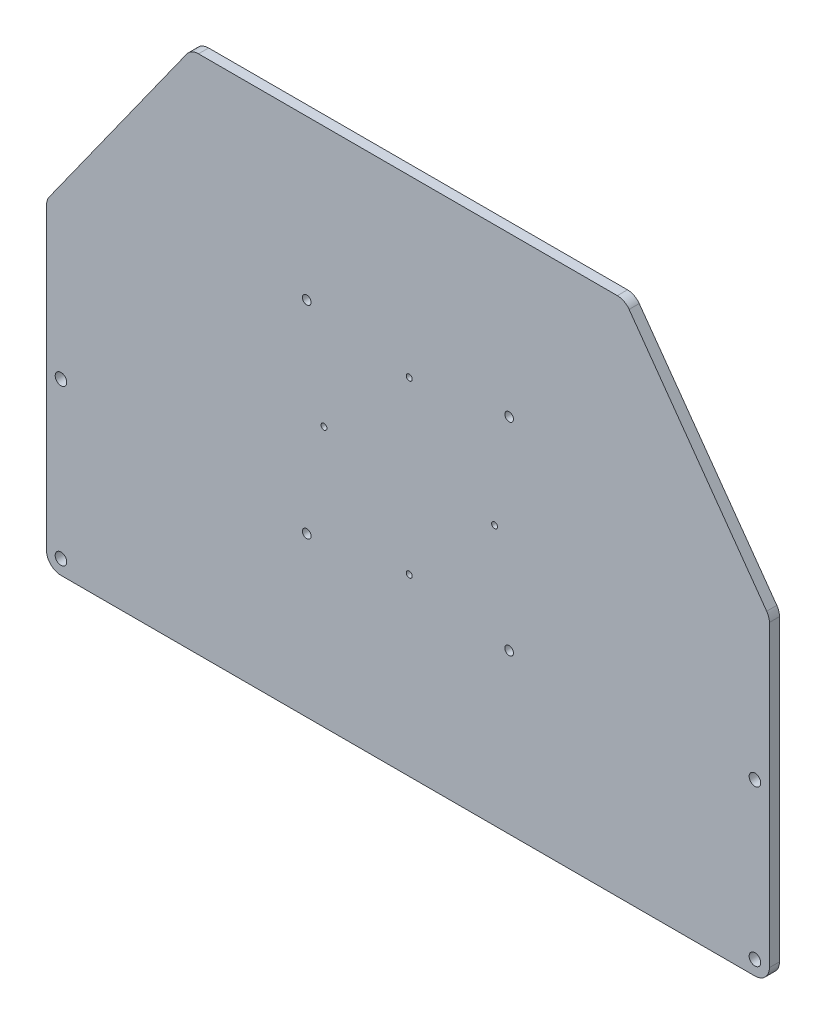
SolidWorks part; units mm, degrees
ref_plane "Plan de face" through (0, 0, 0) normal (0, 0, 1) x (1, 0, 0)
ref_plane "Plan de dessus" through (0, 0, 0) normal (0, 1, 0) x (1, 0, 0)
ref_plane "Plan de droite" through (0, 0, 0) normal (1, 0, 0) x (0, 0, -1)
sketch "Esquisse1" plane through (0, 0, 0) normal (0, 0, 1) x (1, 0, 0)
  line L1 (5, 0) -> (245, 0)
  line L2 (0, 5) -> (0, 305)
  line L3 (0, 305) -> (250, 305)
  line L4 (250, 5) -> (250, 305)
  arc A0 (250, 5) -> (245, 0) centre (245, 5) cw
  arc A1 (5, 0) -> (0, 5) centre (5, 5) cw
  point P7 (250, 0)
  point P10 (0, 0)
  dimension "D2" = 5
  dimension "D3" = 5
  dimension "D1" = 250
  dimension "D4" = 300
extrude "Boss.-Extru.1" add sketch "Esquisse1" along normal blind 3.5
sketch "Esquisse2" plane through (0, 0, 3.5) normal (0, 0, 1) x (1, 0, 0)
  line L0 (-19.0099, 5) -> (402.2953, 5) construction
  line L1 (5, 0) -> (245, 0) construction
  line L2 (5, -25.1291) -> (5, 139.966) construction
  line L3 (0, 305) -> (0, 5) construction
  line L4 (245, -22.1166) -> (245, 94.5536) construction
  line L5 (250, 5) -> (250, 305) construction
  line L6 (-9.3926, 58.8) -> (267.0784, 58.8) construction
  circle A0 centre (5, 5) radius 2
  circle A1 centre (245, 5) radius 2
  circle A2 centre (5, 58.8) radius 2
  circle A3 centre (245, 58.8) radius 2
  dimension "D1" = 4
  dimension "D2" = 4
  dimension "D7" = 4
  dimension "D8" = 4
  dimension "D3" = 5
  dimension "D4" = 5
  dimension "D5" = 5
  dimension "D6" = 53.8
extrude "Enlèv. mat.-Extru.1" cut sketch "Esquisse2" against normal through all
sketch "Esquisse3" plane through (0, 0, 3.5) normal (0, 0, 1) x (1, 0, 0)
  line L0 (0, 110) -> (50, 180)
  line L1 (50, 180) -> (200, 180)
  line L2 (200, 180) -> (250, 110)
  line L3 (125, 632.4465) -> (125, -22.4465) construction
  line L4 (250, 305) -> (0, 305) construction
  line L5 (0, 305) -> (0, 5) construction
  line L6 (250, 5) -> (250, 305) construction
  line L7 (5, 0) -> (245, 0) construction
  point P8 (125, 305)
  point P9 (125, 180)
  dimension "D1" = 110
  dimension "D2" = 110
  dimension "D3" = 150
  dimension "D4" = 180
  dimension "D5" = 180
extrude "Enlèv. mat.-Extru.2" cut sketch "Esquisse3" against normal through all and the other way through all
fillet "Congé1" radius 5 4 edges at (250, 110, 1.75) (200, 180, 1.75) (50, 180, 1.75) (0, 110, 1.75)
sketch "Esquisse4" plane through (0, 0, 0) normal (0, 0, -1) x (-1, 0, 0)
  line L0 (-125, 189.0138) -> (-125, -13.9215) construction
  line L1 (-262.4358, 90) -> (45.4804, 90) construction
  line L3 (-52.5731, 180) -> (-197.4269, 180) construction
  circle A0 centre (-160, 55) radius 1.5
  circle A1 centre (-160, 125) radius 1.5
  circle A2 centre (-90, 125) radius 1.5
  circle A3 centre (-90, 55) radius 1.5
  point P8 (-125, 180)
  dimension "D3" = 3
  dimension "D4" = 3
  dimension "D5" = 3
  dimension "D6" = 3
  dimension "D12" = 35
  dimension "D1" = 70
  dimension "D2" = 70
  dimension "D7" = 70
  dimension "D8" = 70
  dimension "D9" = 35
  dimension "D10" = 35
  dimension "D13" = 90
extrude "Enlèv. mat.-Extru.3" cut sketch "Esquisse4" against normal through all
sketch "Esquisse5" plane through (0, 0, 0) normal (0, 0, -1) x (-1, 0, 0)
  line L0 (-160, 55) -> (-90, 55) construction
  circle A0 centre (-154.962, 90.001) radius 1.025
  circle A1 centre (-95.962, 90.001) radius 1.025
  circle A2 centre (-125.462, 119.502) radius 1.025
  circle A3 centre (-125.462, 60.5) radius 1.025
  dimension "D2" = 41.72
  dimension "D6" = 2.05
  dimension "D7" = 2.05
  dimension "D8" = 2.05
  dimension "D9" = 2.05
  dimension "D10" = 5.5
  dimension "D1" = 59
  dimension "D3" = 41.72
  dimension "D4" = 41.72
  dimension "D5" = 41.72
extrude "Enlèv. mat.-Extru.4" cut sketch "Esquisse5" against normal through all
